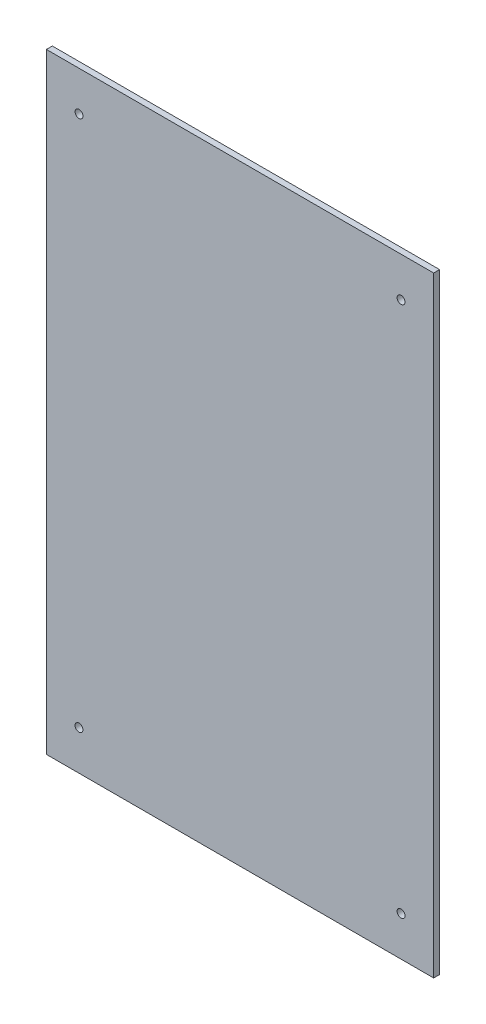
SolidWorks part; units mm, degrees
ref_plane "Plan de face" through (0, 0, 0) normal (0, 0, 1) x (1, 0, 0)
ref_plane "Plan de dessus" through (0, 0, 0) normal (0, 1, 0) x (1, 0, 0)
ref_plane "Plan de droite" through (0, 0, 0) normal (1, 0, 0) x (0, 0, -1)
sketch "Esquisse1" plane through (0, 0, 0) normal (0, 0, 1) x (1, 0, 0)
  line L0 (0, 154.5) -> (0, -154.5) construction
  line L1 (98, 154.5) -> (-98, 154.5)
  line L2 (98, 154.5) -> (98, -154.5)
  line L3 (98, -154.5) -> (-98, -154.5)
  line L4 (-98, 154.5) -> (-98, -154.5)
  line L5 (98, 154.5) -> (-98, -154.5) construction
  line L6 (98, -154.5) -> (-98, 154.5) construction
  line L7 (-98, 0) -> (98, 0) construction
  circle A0 centre (-81.5, 134.5) radius 2
  circle A1 centre (81.5, 134.5) radius 2
  circle A2 centre (81.5, -134.5) radius 2
  circle A3 centre (-81.5, -134.5) radius 2
  point P0 (0, 0)
  dimension "D2" = 4
  dimension "D1" = 163
  dimension "D3" = 309
  dimension "D4" = 196
  dimension "D5" = 20
extrude "Boss.-Extru.1" add sketch "Esquisse1" along normal blind 3
